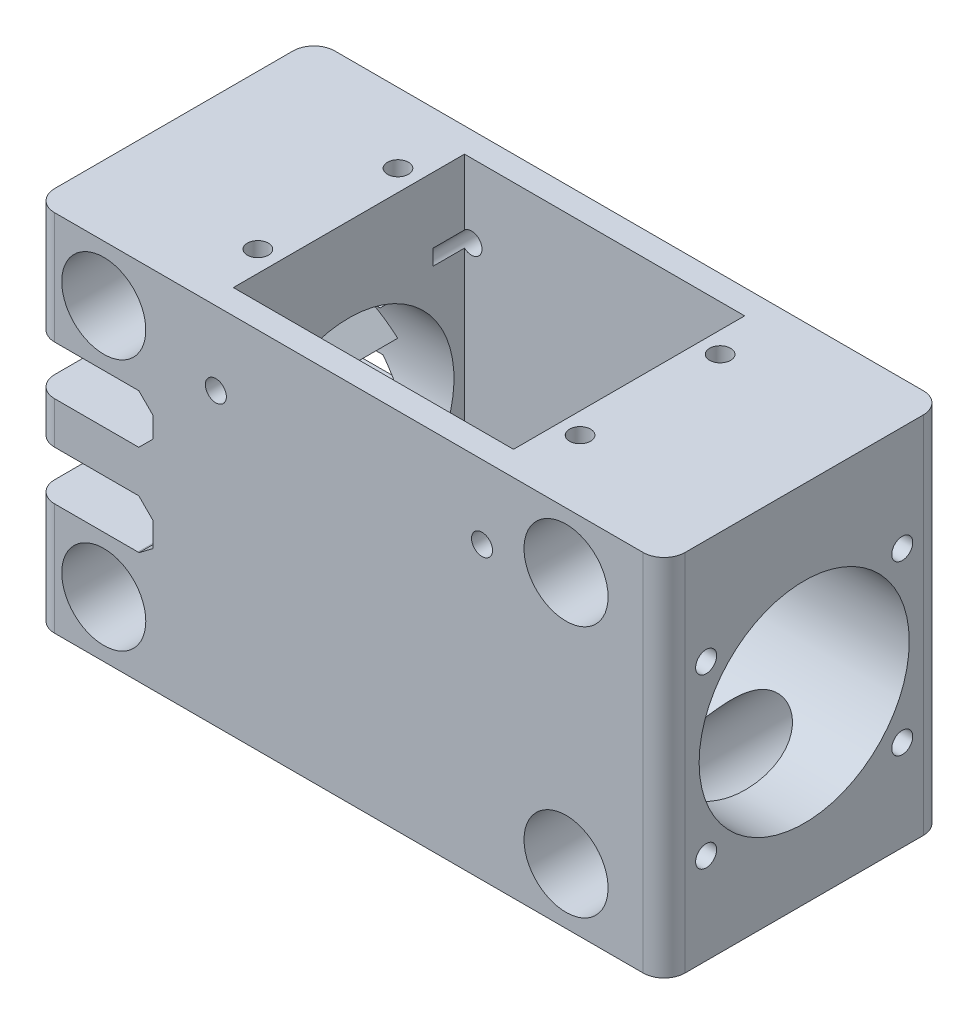
SolidWorks part; units mm, degrees
ref_plane "前基準面" through (0, 0, 0) normal (0, 0, 1) x (1, 0, 0)
ref_plane "上基準面" through (0, 0, 0) normal (0, 1, 0) x (1, 0, 0)
ref_plane "右基準面" through (0, 0, 0) normal (1, 0, 0) x (0, 0, -1)
sketch "草圖1" plane through (0, 0, 0) normal (0, 0, 1) x (1, 0, 0)
  line L1 (-45, 26) -> (45, 26)
  line L2 (-45, 26) -> (-45, -26)
  line L3 (-45, -26) -> (45, -26)
  line L4 (45, 26) -> (45, -26)
  point P5 (0, 26)
  point P6 (45, 0)
  dimension "D1" = 90
  dimension "D2" = 52
extrude "填料-伸長1" add sketch "草圖1" along normal blind 40
sketch "草圖2" plane through (0, 0, 0) normal (0, 0, -1) x (-1, 0, 0)
  line L0 (2, 28) -> (2, -28) construction
  line L3 (-45, 0) -> (45, 0) construction
  line L4 (-45, -26) -> (-45, 26) construction
  line L5 (45, 26) -> (45, -26) construction
  circle A0 centre (-31, -18) radius 6
  circle A1 centre (35, -18) radius 6
  circle A2 centre (35, 18) radius 6
  circle A3 centre (-31, 18) radius 6
  dimension "D1" = 12
  dimension "D2" = 33
  dimension "D3" = 18
  dimension "D4" = 2
extrude "除料-伸長1" cut sketch "草圖2" against normal through all
sketch "草圖6" plane through (0, 0, 0) normal (0, 0, -1) x (-1, 0, 0)
  line L0 (45, -26) -> (-45, -26) construction
  line L1 (-22.5, 19) -> (22.5, 19) construction
  line L2 (-22.5, 19) -> (-22.5, -26) construction
  line L3 (-22.5, -26) -> (22.5, -26) construction
  line L4 (22.5, 19) -> (22.5, -26) construction
  circle A0 centre (-19, 15.5) radius 1.5
  circle A1 centre (19, 15.5) radius 1.5
  point P4 (0, 19)
  dimension "D4" = 3
  dimension "D8" = 3
  dimension "D1" = 45
  dimension "D2" = 45
  dimension "D3" = 3.5
  dimension "D5" = 3.5
  dimension "D6" = 3.5
  dimension "D7" = 3.5
  dimension "D9" = 38
extrude "除料-伸長4" cut sketch "草圖6" against normal blind 8
sketch "草圖8" plane through (0, 0, 0) normal (0, 0, -1) x (-1, 0, 0)
  line L0 (45, 26) -> (45, -26) construction
  line L1 (28, 10) -> (45, 10)
  line L2 (28, 10) -> (28, -10)
  line L3 (28, -10) -> (45, -10)
  line L4 (45, 10) -> (45, -10)
  point P6 (28, 0)
  dimension "D1" = 20
  dimension "D2" = 17
extrude "除料-伸長5" cut sketch "草圖8" against normal through all
sketch "草圖9" plane through (45, 0, 0) normal (1, 0, 0) x (0, 0, -1)
  line L0 (-20, 26) -> (-20, -26) construction
  line L1 (-40, 26) -> (0, 26) construction
  line L2 (-40, -26) -> (0, -26) construction
  circle A0 centre (-20, -1) radius 15
  dimension "D1" = 30
  dimension "D3" = 27
  dimension "D2" = 25
extrude "除料-伸長6" cut sketch "草圖9" against normal through all
sketch "草圖10" plane through (45, 0, 0) normal (1, 0, 0) x (0, 0, -1)
  line L0 (-20, 14) -> (-20, -16) construction
  line L1 (-35, -1) -> (-5, -1) construction
  line L3 (-37, 14) -> (-3, 14) construction
  line L4 (-37, 14) -> (-37, -20) construction
  line L5 (-37, -20) -> (-3, -20) construction
  line L6 (-3, 14) -> (-3, -20) construction
  circle A0 centre (-34, 11) radius 1.5
  circle A1 centre (-6, 11) radius 1.5
  circle A2 centre (-6, -13) radius 1.5
  circle A3 centre (-34, -13) radius 1.5
  circle A4 centre (-20, -1) radius 15 construction
  point P6 (-20, -1)
  point P9 (-20, -1)
  dimension "D3" = 3
  dimension "D1" = 30
  dimension "D2" = 30
  dimension "D4" = 3
  dimension "D5" = 3
extrude "除料-伸長7" cut sketch "草圖10" against normal blind 7
sketch "草圖11" plane through (-45, 0, 0) normal (-1, 0, 0) x (0, 0, 1)
  line L0 (8, -10) -> (32, -10)
  arc A0 (8, -10) -> (32, -10) centre (20, -1) ccw
extrude "填料-伸長4" add sketch "草圖11" against normal blind 22
sketch "草圖14" plane through (0, 0, 0) normal (0, 0, -1) x (-1, 0, 0)
  circle A0 centre (-31, -18) radius 6
  circle A1 centre (35, -18) radius 6
extrude "除料-伸長8" cut sketch "草圖14" against normal through all
sketch "草圖17" plane through (0, -26, 0) normal (0, -1, 0) x (1, 0, 0)
  line L2 (20, 36.5) -> (-20, 36.5)
  line L3 (20, 36.5) -> (20, 3.5)
  line L4 (20, 3.5) -> (-20, 3.5)
  line L5 (-45, 20) -> (45, 20) construction
  line L7 (-45, 40) -> (-45, 0) construction
  line L8 (45, 40) -> (45, 0) construction
  line L9 (0, 40) -> (0, 0) construction
  line L10 (-45, 40) -> (45, 40) construction
  line L11 (-45, 0) -> (45, 0) construction
  line L12 (-20, 36.5) -> (-20, 3.5)
  point P5 (20, 20)
  point P6 (0, 36.5)
  dimension "D1" = 33
  dimension "D2" = 40
  dimension "D3" = 25
extrude "除料-伸長9" cut sketch "草圖17" against normal up to surface (52.001 mm away)
chamfer "導角9" distance 1 angle 82 1 edges at (-23, -10, 20)
sketch "草圖19" plane through (-45, 0, 0) normal (-1, 0, 0) x (0, 0, 1)
  line L0 (9.802, 10) -> (30.198, 10)
  arc A0 (30.198, 10) -> (9.802, 10) centre (20, -1) ccw construction
  arc A1 (30.198, 10) -> (9.802, 10) centre (20, -1) ccw
extrude "填料-伸長6" add sketch "草圖19" against normal up to surface (17 mm away) up to face at (-28, -0.0717, 3.5151)
chamfer "導角10" distance 2 angle 64 2 edges at (-28, 14, 20) (-28, 10, 20)
sketch "草圖20" plane through (0, 0, 0) normal (0, 0, -1) x (-1, 0, 0)
  circle A0 centre (35, 18) radius 6
extrude "除料-伸長13" cut sketch "草圖20" against normal through all
sketch "草圖21" plane through (0, 0, 40) normal (0, 0, 1) x (1, 0, 0)
  line L0 (-28, 10) -> (-28, -10.2973) construction
  line L1 (-28, 3) -> (-45, 3)
  line L2 (-28, 3) -> (-28, -3)
  line L3 (-28, -3) -> (-45, -3)
  line L4 (-45, 3) -> (-45, -3)
  line L5 (-45, 26) -> (-45, -26) construction
  line L6 (45, 0) -> (-45, 0) construction
  point P15 (-45, 0)
  dimension "D1" = 6
extrude "填料-伸長7" add sketch "草圖21" against normal up to surface (40 mm away) up to face at (-20.5, 15.5, 0)
fillet "圓角3" radius 3 8 edges at (-45, -18, 0) (-45, -18, 40) (-45, 18, 0) (-45, 18, 40) (-45, 0, 0) (45, 0, 0) (45, 0, 40) (-45, 0, 40)
chamfer "導角12" distance 3 angle 45 2 edges at (-28, -3, 20) (-28, 3, 20)
sketch "草圖24" plane through (0, 0, 40) normal (0, 0, 1) x (1, 0, 0)
  line L0 (-42, -26) -> (42, -26) construction
  line L1 (-22.5, 19) -> (22.5, 19) construction
  line L2 (-22.5, 19) -> (-22.5, -26) construction
  line L3 (-22.5, -26) -> (22.5, -26) construction
  line L4 (22.5, 19) -> (22.5, -26) construction
  circle A0 centre (-19, 15.5) radius 1.5
  circle A1 centre (19, 15.5) radius 1.5
  point P6 (0, 19)
  dimension "D5" = 3
  dimension "D6" = 3
  dimension "D1" = 45
  dimension "D2" = 45
  dimension "D3" = 3.5
  dimension "D4" = 3.5
  dimension "D7" = 3.5
  dimension "D8" = 3.5
extrude "除料-伸長16" cut sketch "草圖24" against normal blind 8
sketch "草圖25" plane through (0, 26, 0) normal (0, 1, 0) x (1, 0, 0)
  line L0 (45, -20) -> (-45, -20) construction
  line L1 (45, -37) -> (45, -3) construction
  line L2 (-45, -37) -> (-45, -3) construction
  line L3 (0, -3.5) -> (0, -36.5) construction
  line L4 (-20, -3.5) -> (20, -3.5) construction
  line L5 (20, -36.5) -> (-20, -36.5) construction
  circle A0 centre (23, -10) radius 1.5
  circle A1 centre (23, -30) radius 1.5
  circle A2 centre (-23, -30) radius 1.5
  circle A3 centre (-23, -10) radius 1.5
  dimension "D1" = 3
  dimension "D2" = 23
  dimension "D3" = 10
extrude "除料-伸長17" cut sketch "草圖25" against normal blind 10
chamfer "導角13" distance 2 angle 45 8 edges at (-28, -10.2973, 4.1144) (-28, -10.2973, 35.8856) (-28, -3, 37.433) (-28, -3, 2.567) (-28, 10, 4.901) (-28, 10, 35.099) (-28, 3, 37.2284) (-28, 3, 2.7716)
